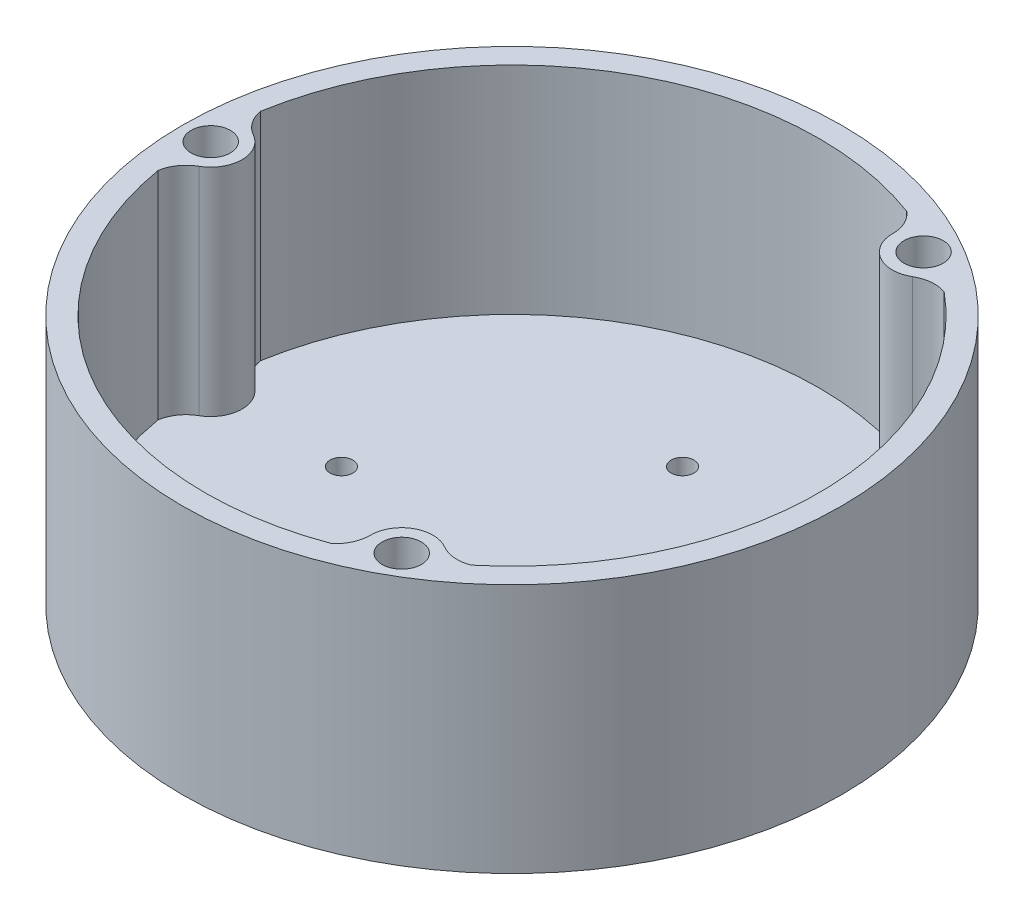
SolidWorks part; units mm, degrees
ref_plane "Front Plane" through (0, 0, 0) normal (0, 0, 1) x (1, 0, 0)
ref_plane "Top Plane" through (0, 0, 0) normal (0, 1, 0) x (1, 0, 0)
ref_plane "Right Plane" through (0, 0, 0) normal (1, 0, 0) x (0, 0, -1)
sketch "Sketch1" plane through (0, 0, 0) normal (0, 1, 0) x (1, 0, 0)
  line L0 (0, 0) -> (0, 15) construction
  line L1 (0, 0) -> (13.25, 22.9497) construction
  circle A0 centre (0, 0) radius 23 construction
  circle A1 centre (0, 0) radius 29
  circle A2 centre (0, 15) radius 1
  circle A3 centre (15, 0) radius 1
  circle A4 centre (0, -15) radius 1
  circle A5 centre (-15, 0) radius 1
  arc A6 (9.4141, 25.3056) -> (-26.6224, 4.5) centre (0, 0) ccw
  circle A7 centre (13.25, 22.9497) radius 1.725
  arc A8 (9.4141, 25.3056) -> (10.5001, 22.9716) centre (7.5002, 22.9954) cw
  arc A9 (10.5001, 22.9716) -> (14.6439, 20.5791) centre (13.25, 22.9497) ccw
  arc A10 (14.6439, 20.5791) -> (17.2083, 20.8056) centre (16.1645, 17.9931) cw
  circle A11 centre (13.25, -22.9497) radius 1.725
  arc A12 (14.6439, -20.5791) -> (10.5001, -22.9716) centre (13.25, -22.9497) ccw
  arc A13 (10.5001, -22.9716) -> (9.4141, -25.3056) centre (7.5002, -22.9954) cw
  arc A14 (17.2083, -20.8056) -> (14.6439, -20.5791) centre (16.1645, -17.9931) cw
  circle A15 centre (-26.5, 0) radius 1.725
  arc A16 (-25.144, -2.3924) -> (-25.144, 2.3924) centre (-26.5, 0) ccw
  arc A17 (-25.144, 2.3924) -> (-26.6224, 4.5) centre (-23.6647, 5.0024) cw
  arc A18 (-26.6224, -4.5) -> (-25.144, -2.3924) centre (-23.6647, -5.0024) cw
  arc A19 (17.2083, -20.8056) -> (17.2083, 20.8056) centre (0, 0) ccw
  arc A21 (-26.6224, -4.5) -> (9.4141, -25.3056) centre (0, 0) ccw
  point P4 (8.3838, 22.9928)
  point P24 (8.9067, 24.4268)
  point P25 (9.8899, 22.7446)
  point P26 (11.875, 20.5681)
  point P44 (16.7009, 19.9372)
  point P45 (15.7204, 18.757)
  point P46 (14.7524, 19.9268)
  point P47 (16.7009, 19.9372)
  point P48 (15.7204, 18.757)
  point P49 (8.3838, 22.9928)
  point P50 (9.4141, 25.3056)
  point P51 (8.8788, 23.8668)
  point P52 (16.2299, 19.5069)
  point P53 (15, 20.5664)
  point P54 (16.2299, 19.6227)
  point P55 (8.8788, 23.9819)
  point P56 (10.3015, 23.2901)
  point P57 (8.8788, 23.8668)
  dimension "D1" = 2
  dimension "D5" = 46
  dimension "D6" = 58
  dimension "D8" = 3.45
  dimension "D10" = 2.75
  dimension "D12" = 3
  dimension "D2" = 15
  dimension "D3" = 4
  dimension "D4" = 2
  dimension "D7" = 26.5
  dimension "D9" = 60
  dimension "D11" = 9
  dimension "D14" = 3
extrude "Boss-Extrude1" add sketch "Sketch1" along normal blind 22 contours A1 A21 A18 A16 A17 A6 A8 A9 A10 A19 A14 A12 A13 A15 A11 A7 | A15 | A7 | A11 region at (-28.918, 0, 0)
extrude "Boss-Extrude2" add sketch "Sketch1<5>" along normal blind 3 contours A18 A21 A13 A12 A14 A19 A10 A9 A8 A6 A17 A16 A2 A3 A4 A5 region at (0, 0, 0)
sketch "Sketch1<5>" plane through (0, 0, 0) normal (0, 1, 0) x (1, 0, 0) same geometry as "Sketch1"
extrude "Cut-Extrude1" cut sketch "Sketch1<6>" against normal blind 3 from surface contours A15 | A7 | A11 starting at face at (0, 22, 0)
sketch "Sketch1<6>" plane through (0, 0, 0) normal (0, 1, 0) x (1, 0, 0) same geometry as "Sketch1"
equation "\"motor-dia\" = 46"
equation "\"motor-holes-rad\" = 15"
equation "\"motor-height\" = 21"
equation "\"motor-case-thickness\" = 2"
equation "\"D2@Sketch1\"=\"motor-holes-rad\""
equation "\"D4@Sketch1\"=\"motor-case-thickness\""
equation "\"D5@Sketch1\"=\"motor-dia\""
equation "\"D1@Boss-Extrude2\"= \"motor-height\" + 1"
equation "\"D1@Boss-Extrude1\"=\"motor-height\"+1"
